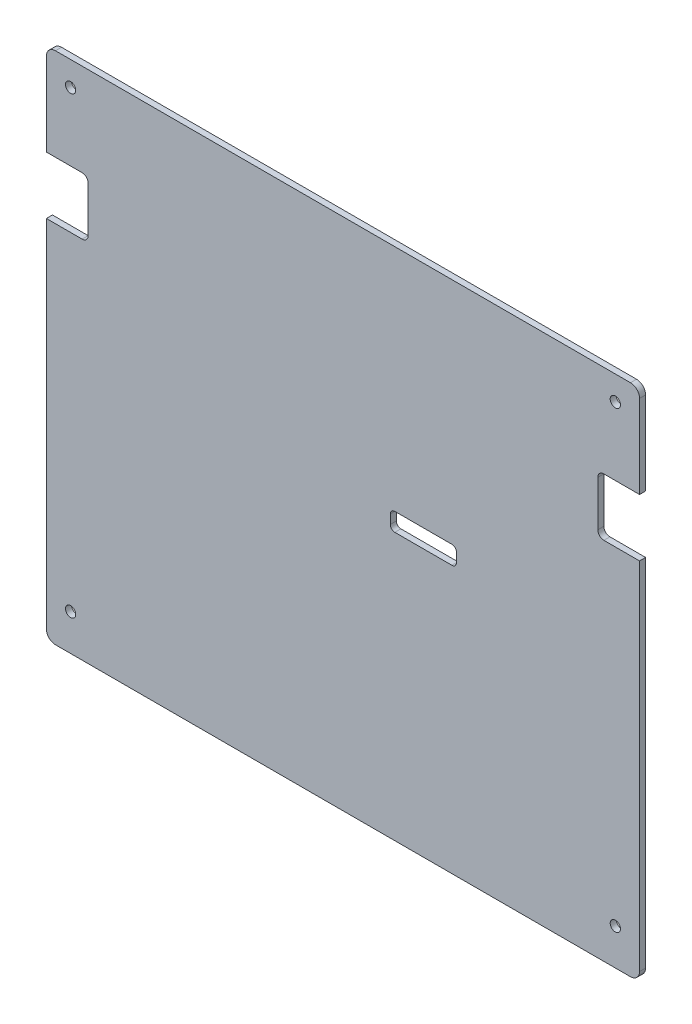
SolidWorks part; units mm, degrees
ref_plane "Спереди" through (0, 0, 0) normal (0, 0, 1) x (1, 0, 0)
ref_plane "Сверху" through (0, 0, 0) normal (0, 1, 0) x (1, 0, 0)
ref_plane "Справа" through (0, 0, 0) normal (1, 0, 0) x (0, 0, -1)
other "Configuration Table"
sketch "Acrylic_2mm_profile" plane through (0, 0, 0) normal (0, 0, 1) x (1, 0, 0)
  line L0 (0, -7) -> (190, -7)
  line L1 (193, -4) -> (193, 160)
  line L2 (190, 163) -> (0, 163)
  line L3 (-3, 160) -> (-3, -4)
  arc A0 (190, -7) -> (193, -4) centre (190, -4) ccw
  arc A1 (193, 160) -> (190, 163) centre (190, 160) ccw
  arc A2 (0, 163) -> (-3, 160) centre (0, 160) ccw
  arc A3 (-3, -4) -> (0, -7) centre (0, -4) ccw
extrude "Acrylic_2mm" add sketch "Acrylic_2mm_profile" along normal blind 2 from offset 12 offset against normal yes
sketch "Hinge_clearance_0_profile" plane through (0, 0, 0) normal (0, 0, 1) x (1, 0, 0)
  line L0 (-4, 113.5) -> (8.8, 113.5)
  line L1 (10.8, 115.5) -> (10.8, 130.5)
  line L2 (8.8, 132.5) -> (-4, 132.5)
  line L3 (-6, 130.5) -> (-6, 115.5)
  arc A0 (8.8, 113.5) -> (10.8, 115.5) centre (8.8, 115.5) ccw
  arc A1 (10.8, 130.5) -> (8.8, 132.5) centre (8.8, 130.5) ccw
  arc A2 (-4, 132.5) -> (-6, 130.5) centre (-4, 130.5) ccw
  arc A3 (-6, 115.5) -> (-4, 113.5) centre (-4, 115.5) ccw
extrude "Hinge_clearance_0" cut sketch "Hinge_clearance_0_profile" against normal blind 2.4 from offset 9.8 offset against normal yes
sketch "Hinge_clearance_1_profile" plane through (0, 0, 0) normal (0, 0, 1) x (1, 0, 0)
  line L0 (181.2, 113.5) -> (194, 113.5)
  line L1 (196, 115.5) -> (196, 130.5)
  line L2 (194, 132.5) -> (181.2, 132.5)
  line L3 (179.2, 130.5) -> (179.2, 115.5)
  arc A0 (194, 113.5) -> (196, 115.5) centre (194, 115.5) ccw
  arc A1 (196, 130.5) -> (194, 132.5) centre (194, 130.5) ccw
  arc A2 (181.2, 132.5) -> (179.2, 130.5) centre (181.2, 130.5) ccw
  arc A3 (179.2, 115.5) -> (181.2, 113.5) centre (181.2, 115.5) ccw
extrude "Hinge_clearance_1" cut sketch "Hinge_clearance_1_profile" against normal blind 2.4 from offset 9.8 offset against normal yes
sketch "M3_clearance_0_profile" plane through (0, 0, 0) normal (0, 0, 1) x (1, 0, 0)
  circle A0 centre (5, 5) radius 1.7
extrude "M3_clearance_0" cut sketch "M3_clearance_0_profile" against normal blind 2.4 from offset 9.8 offset against normal yes
sketch "M3_clearance_1_profile" plane through (0, 0, 0) normal (0, 0, 1) x (1, 0, 0)
  circle A0 centre (185, 5) radius 1.7
extrude "M3_clearance_1" cut sketch "M3_clearance_1_profile" against normal blind 2.4 from offset 9.8 offset against normal yes
sketch "M3_clearance_2_profile" plane through (0, 0, 0) normal (0, 0, 1) x (1, 0, 0)
  circle A0 centre (5, 155) radius 1.7
extrude "M3_clearance_2" cut sketch "M3_clearance_2_profile" against normal blind 2.4 from offset 9.8 offset against normal yes
sketch "M3_clearance_3_profile" plane through (0, 0, 0) normal (0, 0, 1) x (1, 0, 0)
  circle A0 centre (185, 155) radius 1.7
extrude "M3_clearance_3" cut sketch "M3_clearance_3_profile" against normal blind 2.4 from offset 9.8 offset against normal yes
sketch "Keys_access_R1_5_profile" plane through (0, 0, 0) normal (0, 0, 1) x (1, 0, 0)
  line L0 (112.125, 81.25) -> (131, 81.25)
  line L1 (132.5, 82.75) -> (132.5, 85.75)
  line L2 (131, 87.25) -> (112.125, 87.25)
  line L3 (110.625, 85.75) -> (110.625, 82.75)
  arc A0 (131, 81.25) -> (132.5, 82.75) centre (131, 82.75) ccw
  arc A1 (132.5, 85.75) -> (131, 87.25) centre (131, 85.75) ccw
  arc A2 (112.125, 87.25) -> (110.625, 85.75) centre (112.125, 85.75) ccw
  arc A3 (110.625, 82.75) -> (112.125, 81.25) centre (112.125, 82.75) ccw
extrude "Keys_access_R1_5" cut sketch "Keys_access_R1_5_profile" against normal blind 2.4 from offset 9.8 offset against normal yes
